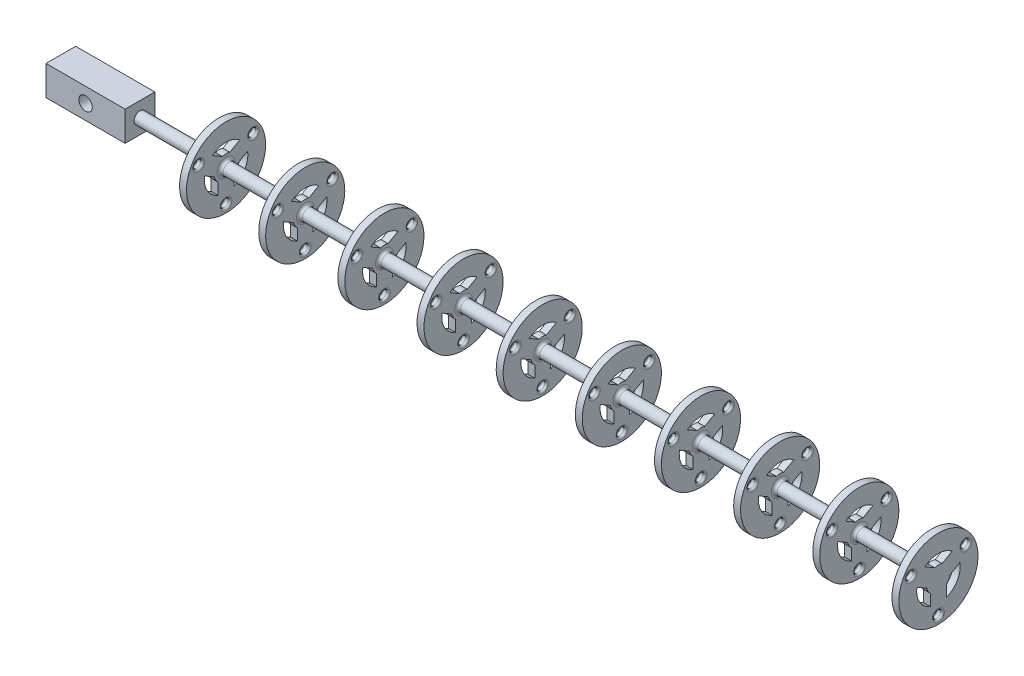
SolidWorks part; units mm, degrees
ref_plane "Front Plane" through (0, 0, 0) normal (0, 0, 1) x (1, 0, 0)
ref_plane "Top Plane" through (0, 0, 0) normal (0, 1, 0) x (1, 0, 0)
ref_plane "Right Plane" through (0, 0, 0) normal (1, 0, 0) x (0, 0, -1)
sketch "Sketch2" plane through (0, 0, 0) normal (0, 0, 1) x (1, 0, 0)
  line L0 (0, 1.5) -> (200, 1.5)
  line L1 (0, -11) -> (0, 11) construction
  line L2 (200, 1.5) -> (200, 0)
  line L3 (200, 0) -> (0, 0)
  line L4 (0, 0) -> (0, 1.5)
  dimension "D1" = 1.5
  dimension "D2" = 200
  dimension "D3" = 1.5
revolve "Revolve1" add sketch "Sketch2" angle 360 about L3
ref_axis "Axis1" through (-3.9062, 0, 0) along (1, 0, 0)
sketch "Sketch3" plane through (0, 0, 0) normal (0, 0, 1) x (1, 0, 0)
  line L0 (20, 0) -> (20, 10)
  line L1 (20, 10) -> (21.75, 10)
  line L2 (21.75, 10) -> (21.75, 0)
  line L3 (21.75, 0) -> (20, 0)
  line L4 (0, -11) -> (0, 11) construction
  dimension "D1" = 1.75
  dimension "D2" = 10
  dimension "D3" = 20
revolve "Revolve2" add sketch "Sketch3" angle 360 about L3
sketch "Sketch5" plane through (21.75, 0, 0) normal (1, 0, 0) x (0, 0, -1)
  line L0 (0, -8) -> (0, 0) construction
  line L1 (0, 0) -> (6.9282, 4) construction
  line L2 (-6.9282, 4) -> (0, 0) construction
  line L3 (0, 11) -> (0, -11) construction
  line L4 (-3.4371, 4.2938) -> (-0.9365, 2.8501)
  line L5 (0.9365, 2.8501) -> (3.4371, 4.2938)
  line L6 (2, -2.2361) -> (2, -5.1235)
  line L7 (5.4371, 0.8297) -> (2.9365, -0.614)
  line L8 (-2.9365, -0.614) -> (-5.4371, 0.8297)
  line L9 (-2, -5.1235) -> (-2, -2.2361)
  circle A0 centre (0, -8) radius 1
  circle A1 centre (6.9282, 4) radius 1
  circle A2 centre (-6.9282, 4) radius 1
  arc A3 (-3.4371, 4.2938) -> (3.4371, 4.2938) centre (0, 0) cw
  circle A6 centre (0, 0) radius 10 construction
  arc A8 (-0.9365, 2.8501) -> (0.9365, 2.8501) centre (0, 0) cw
  circle A9 centre (0, 0) radius 1.5 construction
  arc A10 (5.4371, 0.8297) -> (2, -5.1235) centre (0, 0) cw
  arc A11 (2.9365, -0.614) -> (2, -2.2361) centre (0, 0) cw
  arc A12 (-2, -5.1235) -> (-5.4371, 0.8297) centre (0, 0) cw
  arc A13 (-2, -2.2361) -> (-2.9365, -0.614) centre (0, 0) cw
  point P29 (0, 0)
  dimension "D2" = 2
  dimension "D1" = 8
  dimension "D3" = 120
  dimension "D4" = 120
  dimension "D6" = 2
  dimension "D7" = 4.5
  dimension "D5" = 1.5
  dimension "D8" = 3
extrude "Cut-Extrude1" cut sketch "Sketch5" against normal up to next
fillet "Fillet1" radius 0.5 6 edges at (20, 3, -6.9282) (20, -9, 0) (21.75, -7, 0) (21.75, 5, -6.9282) (20, 3, 6.9282) (21.75, 5, 6.9282)
pattern_linear "LPattern1" count 10 spacing 20 along (1, 0, 0) of "Revolve2", "Cut-Extrude1", "Fillet1"
sketch "Sketch16" plane through (0, 0, 0) normal (-1, 0, 0) x (0, 0, 1)
  line L1 (-3.75, -3.75) -> (3.75, -3.75)
  line L2 (-3.75, -3.75) -> (-3.75, 3.75)
  line L3 (-3.75, 3.75) -> (3.75, 3.75)
  line L4 (3.75, -3.75) -> (3.75, 3.75)
  line L5 (-3.75, -3.75) -> (3.75, 3.75) construction
  line L6 (-3.75, 3.75) -> (3.75, -3.75) construction
  point P0 (0, 0)
  dimension "D1" = 7.5
extrude "Boss-Extrude1" add sketch "Sketch16" along normal blind 20
sketch "Sketch19" plane through (0, 0, -3.75) normal (0, 0, -1) x (-1, 0, 0)
  line L0 (3.9062, 0) -> (-200, 0) construction
  line L1 (20, 3.75) -> (0, 3.75) construction
  line L2 (20, 3.75) -> (20, -3.75) construction
  point P0 (10, 0)
  point P7 (10, 3.75)
  point P10 (20, 0)
hole_wizard "M3 Clearance Hole1" positions "Sketch19" profile "Sketch18" hole size "M3" standard "ANSI Metric" end condition through all
sketch "Sketch18" plane through (-10, 0, -3.75) normal (1, 0, 0) x (0, 1, 0)
  line L0 (0, 0) -> (0, 13.75)
  line L1 (0, 13.75) -> (1.7, 13.75)
  line L2 (1.7, 13.75) -> (1.7, 0.025)
  line L3 (1.7, 0.025) -> (1.725, 0)
  line L5 (1.725, 0) -> (0, 0)
  line L6 (-1.7, 0.025) -> (-1.725, 0) construction
  line L11 (0, -6.35) -> (0, 107.95) construction
  dimension "Thru Hole Dia." = 3.4
  dimension "Thru Hole Depth" = 13.75
  dimension "Near C'Sink Dia." = 3.45
  dimension "Near C'Sink Angle" = 90
fillet "Fillet2" radius 0.75 19 edges at (20, -1.5, 0) (21.75, 1.5, 0) (40, -1.5, 0) (41.75, 1.5, 0) (60, -1.5, 0) (61.75, 1.5, 0) (80, -1.5, 0) (81.75, 1.5, 0) (100, -1.5, 0) (101.75, 1.5, 0) (120, -1.5, 0) (121.75, 1.5, 0) (140, -1.5, 0) (141.75, 1.5, 0) (160, -1.5, 0) (161.75, 1.5, 0) (180, -1.5, 0) (181.75, 1.5, 0) (200, 1.5, 0)
equation "\"R_initial\" = 1.5"
equation "\"D1@Sketch2\"=\"R_initial\""
equation "\"R_distal\" = 1.5"
equation "\"D3@Sketch2\"=\"R_distal\""
equation "\"L\"=200"
equation "\"D2@Sketch2\"=\"L\""
equation "\"disk_thickness\"= 1.75"
equation "\"D1@Sketch3\"=\"disk_thickness\""
equation "\"disk_radius\"= 10"
equation "\"D2@Sketch3\"=\"disk_radius\""
equation "\"disk_spacing_initial\"= 20"
equation "\"D3@Sketch3\"=\"disk_spacing_initial\""
equation "\"tendon_routing_radius\"= 8"
equation "\"D1@Sketch5\"=\"tendon_routing_radius\""
equation "\"tendon_routing_hole_radius\"=2"
equation "\"D2@Sketch5\"=\"tendon_routing_hole_radius\""
equation "\"tendon_routing_hole_fillet\"=0.5"
equation "\"D1@Fillet1\"=\"tendon_routing_hole_fillet\""
equation "\"inter_disk_spacing\"= 20"
equation "\"D3@LPattern1\"=\"inter_disk_spacing\""
equation "\"num_disk\"= 10"
equation "\"D1@LPattern1\"=\"num_disk\""
